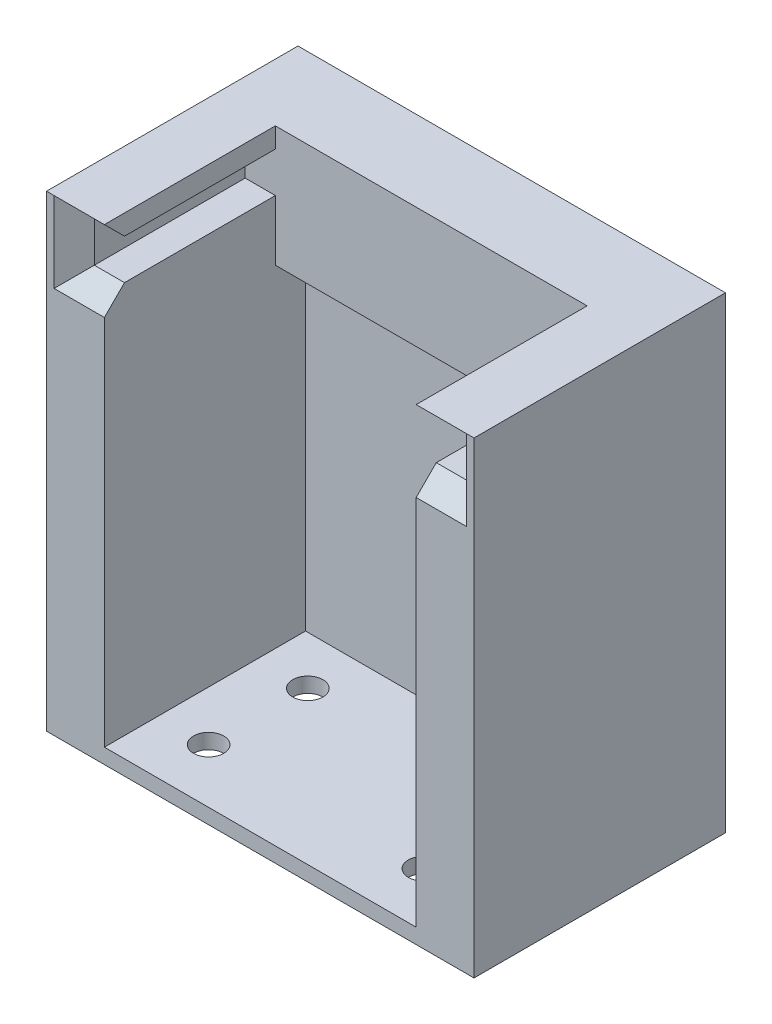
SolidWorks part; units mm, degrees
ref_plane "Front Plane" through (0, 0, 0) normal (0, 0, 1) x (1, 0, 0)
ref_plane "Top Plane" through (0, 0, 0) normal (0, 1, 0) x (1, 0, 0)
ref_plane "Right Plane" through (0, 0, 0) normal (1, 0, 0) x (0, 0, -1)
sketch "Sketch1" plane through (0, 0, 0) normal (0, 1, 0) x (1, 0, 0)
  line L1 (-85, 0) -> (0, 0)
  line L2 (-85, 0) -> (-85, -50)
  line L3 (-85, -50) -> (0, -50)
  line L4 (0, 0) -> (0, -50)
  dimension "D1" = 85
  dimension "D2" = 50
extrude "Boss-Extrude1" add sketch "Sketch1" along normal blind 90
sketch "Sketch2" plane through (0, 90, 0) normal (0, 1, 0) x (1, 0, 0)
  line L0 (-85, -50) -> (0, -50) construction
  line L1 (-73.5, -50) -> (-11.5, -50)
  line L2 (-73.5, -50) -> (-73.5, -10)
  line L3 (-73.5, -10) -> (-11.5, -10)
  line L4 (-11.5, -50) -> (-11.5, -10)
  line L6 (-85, 0) -> (-85, -50) construction
  dimension "D1" = 62
  dimension "D2" = 11.5
  dimension "D3" = 40
extrude "Cut-Extrude1" cut sketch "Sketch2" against normal up to next
sketch "Sketch3" plane through (0, 90, 0) normal (0, 1, 0) x (1, 0, 0)
  line L0 (-85, 0) -> (-85, -50) construction
  line L1 (-85, 0) -> (0, 0)
  line L2 (-85, 0) -> (-85, -16)
  line L3 (-85, -16) -> (0, -16)
  line L4 (0, 0) -> (0, -16)
  line L5 (0, 0) -> (-85, 0) construction
  line L6 (0, -50) -> (0, 0) construction
  dimension "D1" = 16
extrude "Boss-Extrude2" add sketch "Sketch3" against normal blind 24
sketch "Sketch4" plane through (0, 0, 16) normal (0, 0, 1) x (1, 0, 0)
  line L0 (-73.5, 0) -> (-73.5, 90) construction
  line L1 (-73.5, 86) -> (-79.5, 86)
  line L2 (-73.5, 86) -> (-73.5, 78)
  line L3 (-73.5, 78) -> (-79.5, 78)
  line L4 (-79.5, 86) -> (-79.5, 78)
  line L5 (-11.5, 0) -> (-11.5, 90) construction
  line L6 (-11.5, 86) -> (-5.5, 86)
  line L7 (-11.5, 86) -> (-11.5, 78)
  line L8 (-11.5, 78) -> (-5.5, 78)
  line L9 (-5.5, 86) -> (-5.5, 78)
  line L10 (-85, 90) -> (-73.5, 90) construction
  dimension "D1" = 6
  dimension "D2" = 6
  dimension "D3" = 8
  dimension "D4" = 4
extrude "Cut-Extrude2" cut sketch "Sketch4" along normal up to next
sketch "Sketch5" plane through (0, 0, 0) normal (0, -1, 0) x (1, 0, 0)
  line L0 (-85, 0) -> (-85, 50) construction
  line L1 (-85, 0) -> (0, 0)
  line L2 (-85, 0) -> (-85, 50)
  line L3 (-85, 50) -> (0, 50)
  line L4 (0, 0) -> (0, 50)
extrude "Boss-Extrude3" add sketch "Sketch5" along normal blind 3
sketch "Sketch6" plane through (0, 0, 0) normal (0, 1, 0) x (1, 0, 0)
  circle A0 centre (-63.4065, -19.6402) radius 3
  circle A1 centre (-20.8611, -19.6402) radius 3
  circle A2 centre (-20.8611, -39.2024) radius 3
  circle A3 centre (-63.5718, -39.2024) radius 3
  point P8 (-66.336, -19.041)
  point P9 (-66.336, -45.0076)
  point P10 (-18.0647, -45.0076)
  point P11 (-18.0647, -19.041)
  point P12 (-63.4065, -19.6402)
  point P13 (-63.4065, -43.4763)
  point P14 (-20.8611, -43.4763)
  point P15 (-20.8611, -19.041)
  point P16 (-20.8611, -19.6402)
  point P17 (0, 0)
  point P18 (-20.8611, -39.2766)
  point P19 (0, 0)
  point P20 (-20.8611, -39.2024)
  dimension "D1" = 6
extrude "Cut-Extrude3" cut sketch "Sketch6" against normal up to next
chamfer "Chamfer1" distance 4 angle 45 6 edges at (-8.5, 86, 50) (-5.5, 82, 50) (-8.5, 78, 50) (-76.5, 78, 50) (-79.5, 82, 50) (-76.5, 86, 50)
